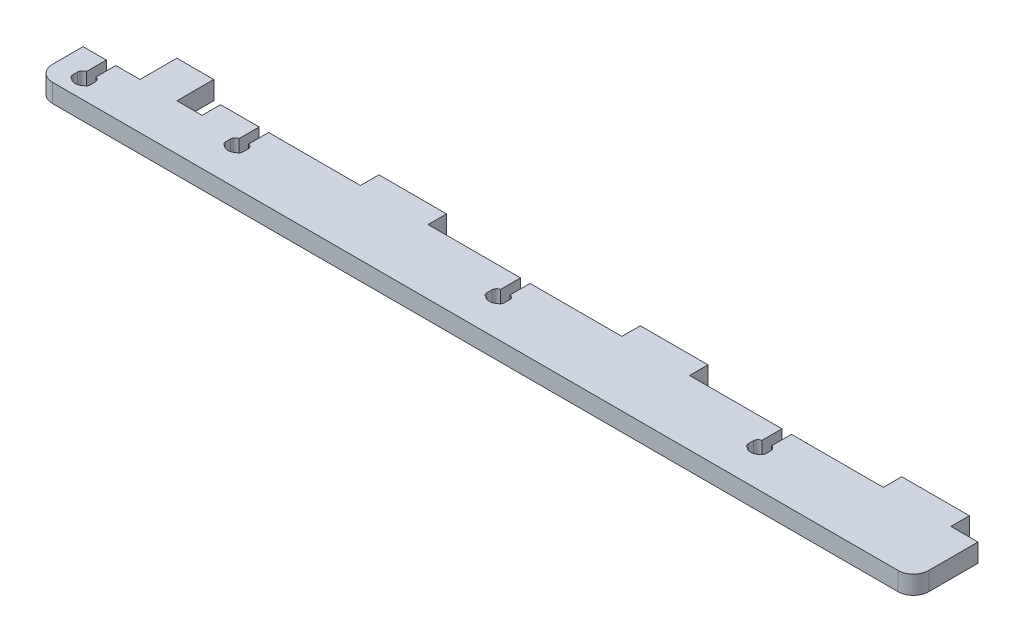
SolidWorks part; units mm, degrees
ref_plane "Alzado" through (0, 0, 0) normal (0, 0, 1) x (1, 0, 0)
ref_plane "Planta" through (0, 0, 0) normal (0, 1, 0) x (1, 0, 0)
ref_plane "Vista lateral" through (0, 0, 0) normal (1, 0, 0) x (0, 0, -1)
sketch "Croquis1" plane through (0, 0, 0) normal (0, 1, 0) x (1, 0, 0)
  line L0 (-113.4766, -5.7424) -> (-113.4766, -11.2465) construction
  line L1 (-122.4766, -5.7424) -> (-114.9266, -5.7424)
  line L2 (-122.4766, -5.7424) -> (-122.4766, -15.7424)
  line L3 (-117.4766, -20.7424) -> (157.5234, -20.7424)
  line L4 (162.5234, -0.7424) -> (162.5234, -15.7424)
  line L5 (-114.9266, -12.2426) -> (-114.9266, -5.7424)
  line L6 (-111.8266, -12.2426) -> (-111.8266, -5.7424)
  line L7 (-110.5363, -13.7707) -> (-110.5363, -15.3207)
  line L8 (-111.2451, -16.6226) -> (-111.4144, -16.6226)
  line L9 (-115.5081, -16.6226) -> (-115.3389, -16.6226)
  line L10 (-116.217, -13.7707) -> (-116.217, -15.3207)
  line L11 (-69.7766, 0.2576) -> (-69.7766, -5.2465) construction
  line L12 (-105.4766, -5.7424) -> (-104.4766, -5.7424)
  line L13 (131.2234, 0.2576) -> (101.8734, 0.2576)
  line L14 (-103.9766, 6.2576) -> (-91.9766, 6.2576)
  line L15 (46.2234, 0.2576) -> (16.8734, 0.2576)
  line L16 (-69.7766, 0.2576) -> (-69.7766, -5.2465) construction
  line L17 (162.5234, -0.7424) -> (162.5234, 0.2576)
  line L18 (162.5234, 0.2576) -> (154.2234, 0.2576)
  line L19 (-83.7766, -5.7424) -> (-83.7766, 0.2576)
  line L20 (-71.2266, -6.2426) -> (-71.2266, 0.2576)
  line L21 (-68.1266, -6.2426) -> (-68.1266, 0.2576)
  line L22 (-66.8363, -7.7707) -> (-66.8363, -9.3207)
  line L23 (-67.5451, -10.6226) -> (-67.7144, -10.6226)
  line L24 (-71.8081, -10.6226) -> (-71.6389, -10.6226)
  line L25 (-72.517, -7.7707) -> (-72.517, -9.3207)
  line L26 (46.7234, 6.2576) -> (68.7234, 6.2576)
  line L27 (-39.7766, 0.2576) -> (-38.7766, 0.2576)
  line L28 (-15.7766, 0.2576) -> (-14.7766, 0.2576)
  line L29 (-38.2766, 6.2576) -> (-16.2766, 6.2576)
  line L30 (-38.7766, 0.2576) -> (-68.1266, 0.2576)
  line L31 (-91.4766, -5.7424) -> (-90.4766, -5.7424)
  line L32 (-91.4766, -5.7424) -> (-83.7766, -5.7424)
  line L33 (13.7734, -6.2426) -> (13.7734, 0.2576)
  line L34 (16.8734, -6.2426) -> (16.8734, 0.2576)
  line L35 (18.1637, -7.7707) -> (18.1637, -9.3207)
  line L36 (17.4549, -10.6226) -> (17.2856, -10.6226)
  line L37 (13.1919, -10.6226) -> (13.3611, -10.6226)
  line L38 (12.483, -7.7707) -> (12.483, -9.3207)
  line L39 (15.2234, 0.2576) -> (15.2234, -5.2465) construction
  line L40 (15.2234, 0.2576) -> (15.2234, -5.2465) construction
  line L41 (131.7234, 6.2576) -> (153.7234, 6.2576)
  line L42 (-104.4766, -5.7424) -> (-103.9766, -5.7424)
  line L43 (-103.9766, 6.2576) -> (-103.9766, -5.7424)
  line L44 (98.7734, -6.2426) -> (98.7734, 0.2576)
  line L45 (101.8734, -6.2426) -> (101.8734, 0.2576)
  line L46 (103.1637, -7.7707) -> (103.1637, -9.3207)
  line L47 (102.4549, -10.6226) -> (102.2856, -10.6226)
  line L48 (98.1919, -10.6226) -> (98.3611, -10.6226)
  line L49 (97.483, -7.7707) -> (97.483, -9.3207)
  line L50 (100.2234, 0.2576) -> (100.2234, -5.2465) construction
  line L51 (100.2234, 0.2576) -> (100.2234, -5.2465) construction
  line L52 (-71.2266, 0.2576) -> (-83.7766, 0.2576)
  line L53 (-111.8266, -5.7424) -> (-104.4766, -5.7424)
  line L54 (13.7734, 0.2576) -> (-15.7766, 0.2576)
  line L55 (98.7734, 0.2576) -> (69.2234, 0.2576)
  line L56 (-91.9766, -5.7424) -> (-91.4766, -5.7424)
  line L58 (-38.7766, 0.2576) -> (-38.2766, 0.2576)
  line L59 (-16.2766, 0.2576) -> (-15.7766, 0.2576)
  line L60 (-16.2766, 0.2576) -> (-15.7766, 0.2576)
  line L61 (-104.4766, -5.7424) -> (-103.9766, -5.7424)
  line L62 (-91.9766, -5.7424) -> (-91.4766, -5.7424)
  line L64 (-91.9766, 6.2576) -> (-91.9766, -5.7424)
  line L65 (-38.7766, 0.2576) -> (-38.2766, 0.2576)
  line L66 (-38.2766, 6.2576) -> (-38.2766, 0.2576)
  line L67 (-16.2766, 6.2576) -> (-16.2766, 0.2576)
  line L68 (46.7234, 6.2576) -> (46.7234, 0.2576)
  line L69 (68.7234, 6.2576) -> (68.7234, 0.2576)
  line L70 (131.7234, 6.2576) -> (131.7234, 0.2576)
  line L71 (153.7234, 6.2576) -> (153.7234, 0.2576)
  line L72 (46.2234, 0.2576) -> (46.7234, 0.2576)
  line L73 (68.7234, 0.2576) -> (69.2234, 0.2576)
  line L74 (131.2234, 0.2576) -> (131.7234, 0.2576)
  line L75 (153.7234, 0.2576) -> (154.2234, 0.2576)
  arc A0 (-110.5363, -13.7707) -> (-111.8266, -12.2426) centre (-112.0863, -13.7707) ccw
  arc A1 (-111.2451, -16.6226) -> (-110.5363, -15.3207) centre (-112.0863, -15.3207) ccw
  arc A2 (-115.3389, -16.6226) -> (-111.4144, -16.6226) centre (-113.3766, -14.6611) ccw
  arc A3 (-115.5081, -16.6226) -> (-116.217, -15.3207) centre (-114.667, -15.3207) cw
  arc A4 (-116.217, -13.7707) -> (-114.9266, -12.2426) centre (-114.667, -13.7707) cw
  arc A5 (-66.8363, -7.7707) -> (-68.1266, -6.2426) centre (-68.3863, -7.7707) ccw
  arc A6 (-67.5451, -10.6226) -> (-66.8363, -9.3207) centre (-68.3863, -9.3207) ccw
  arc A7 (-71.6389, -10.6226) -> (-67.7144, -10.6226) centre (-69.6766, -8.6611) ccw
  arc A8 (-71.8081, -10.6226) -> (-72.517, -9.3207) centre (-70.967, -9.3207) cw
  arc A9 (-72.517, -7.7707) -> (-71.2266, -6.2426) centre (-70.967, -7.7707) cw
  arc A10 (18.1637, -7.7707) -> (16.8734, -6.2426) centre (16.6137, -7.7707) ccw
  arc A11 (17.4549, -10.6226) -> (18.1637, -9.3207) centre (16.6137, -9.3207) ccw
  arc A12 (13.3611, -10.6226) -> (17.2856, -10.6226) centre (15.3234, -8.6611) ccw
  arc A13 (13.1919, -10.6226) -> (12.483, -9.3207) centre (14.033, -9.3207) cw
  arc A14 (12.483, -7.7707) -> (13.7734, -6.2426) centre (14.033, -7.7707) cw
  arc A15 (103.1637, -7.7707) -> (101.8734, -6.2426) centre (101.6137, -7.7707) ccw
  arc A16 (102.4549, -10.6226) -> (103.1637, -9.3207) centre (101.6137, -9.3207) ccw
  arc A17 (98.3611, -10.6226) -> (102.2856, -10.6226) centre (100.3234, -8.6611) ccw
  arc A18 (98.1919, -10.6226) -> (97.483, -9.3207) centre (99.033, -9.3207) cw
  arc A19 (97.483, -7.7707) -> (98.7734, -6.2426) centre (99.033, -7.7707) cw
  arc A20 (162.5234, -15.7424) -> (157.5234, -20.7424) centre (157.5234, -15.7424) cw
  arc A21 (-122.4766, -15.7424) -> (-117.4766, -20.7424) centre (-117.4766, -15.7424) ccw
  point P6 (-113.4766, -5.7424)
  point P35 (-69.7766, 0.2576)
  point P109 (162.5234, -20.7424)
  point P112 (-122.4766, -20.7424)
  dimension "D15" = 5
  dimension "D1" = 285
  dimension "D3" = 9
  dimension "D7" = 6
  dimension "D13" = 3
  dimension "D16" = 15
  dimension "D21" = 3
extrude "Saliente-Extruir1" add sketch "Croquis1" along normal blind 6 contours L2 A21 L3 A20 L4 L17 L18 L41 L13 L45 A15 L46 A16 L47 A17 L48 A18 L49 A19 L44 L55 L26 L15 L34 A10 L35 A11 L36 A12 L37 A13 L38 A14 L33 L54 L28 L29 L27 L30 L21 A5 L22 A6 L23 A7 region at (25.4791, 0, 9.464)
